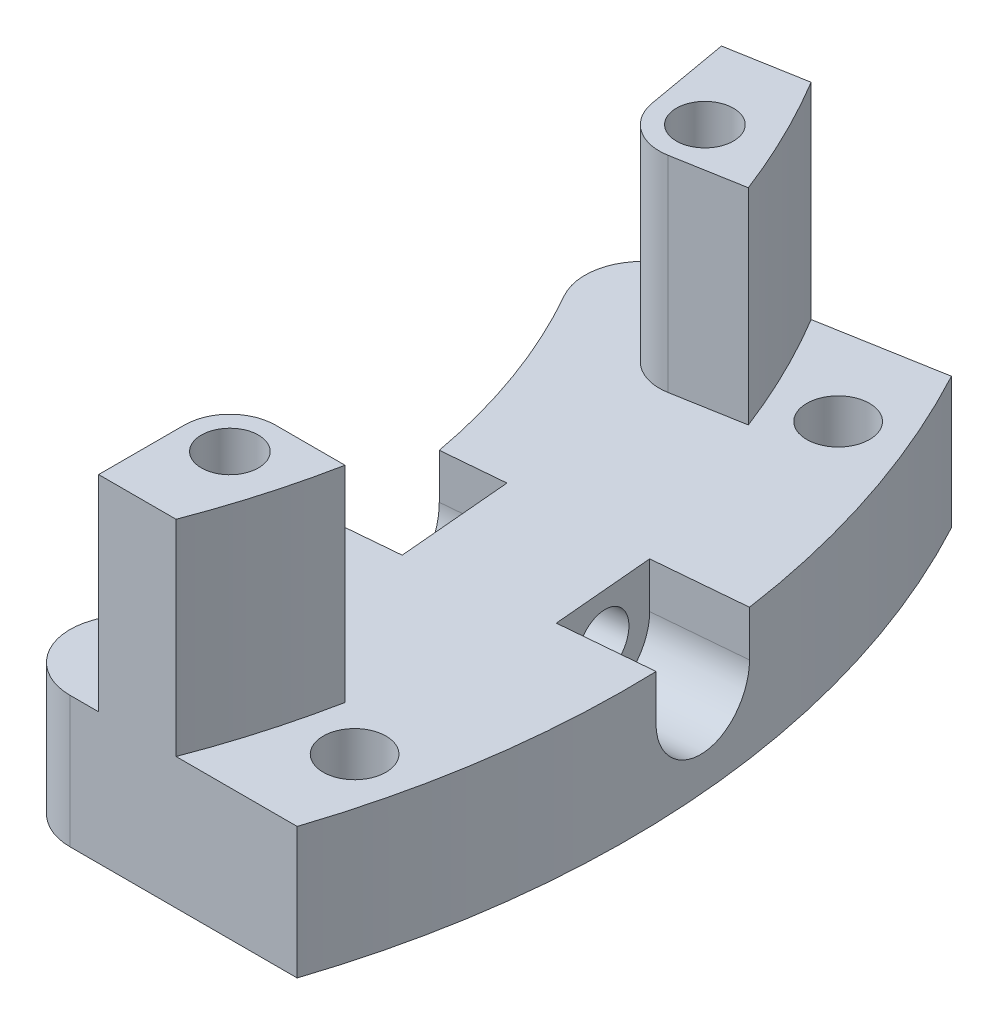
SolidWorks part; units mm, degrees
ref_plane "Front Plane" through (0, 0, 0) normal (0, 0, 1) x (1, 0, 0)
ref_plane "Top Plane" through (0, 0, 0) normal (0, 1, 0) x (1, 0, 0)
ref_plane "Right Plane" through (0, 0, 0) normal (1, 0, 0) x (0, 0, -1)
sketch "Sketch1" plane through (0, 0, 0) normal (0, 1, 0) x (1, 0, 0)
  line L0 (48.4934, -25) -> (75.9934, -25)
  line L1 (43.4155, 33.041) -> (70.4977, 37.8163)
  line L2 (0, -25) -> (48.4934, -25) construction
  line L3 (11.1696, 27.3552) -> (43.4155, 33.041) construction
  line L4 (-4.3412, 24.6202) -> (70.4977, 37.8163) construction
  arc A0 (70.4977, 37.8163) -> (75.9934, -25) centre (0, 0) cw
  arc A1 (43.4155, 33.041) -> (48.4934, -25) centre (0, 0) cw
  circle A2 centre (0, 0) radius 25 construction
  arc A3 (-4.3412, 24.6202) -> (0, -25) centre (0, 0) ccw construction
  point P3 (0, 0)
  point P9 (0, 32.5)
  point P10 (0, 0)
  point P13 (28.4664, 0.9627)
  point P17 (-8.5505, 23.4923)
  point P18 (10.6204, 30.47)
  dimension "D1" = 80
  dimension "D3" = 27.5
  dimension "D4" = 50
extrude "Boss-Extrude1" add sketch "Sketch1" along normal blind 11.5
sketch "Sketch2" plane through (0, 11.5, 0) normal (0, -1, 0) x (1, 0, 0)
  line L0 (48.4934, 25) -> (75.9934, 25) construction
  line L1 (70.4977, -37.8163) -> (43.4155, -33.041) construction
  line L2 (70.4977, -37.8163) -> (43.4155, -33.041) construction
  line L3 (62.5999, 13.5) -> (68.6859, 13.5)
  line L4 (58.5999, 17.5) -> (58.5999, 25)
  line L5 (48.4934, 25) -> (75.9934, 25) construction
  line L6 (58.5999, 25) -> (65.3835, 25)
  line L7 (54.6708, -27.4099) -> (53.3685, -34.796)
  line L8 (59.3046, -24.1653) -> (65.2981, -25.2221)
  line L9 (60.049, -35.9739) -> (53.3685, -34.796)
  arc A0 (65.3835, 25) -> (60.049, -35.9739) centre (0, 0) cw construction
  arc A1 (70.4977, -37.8163) -> (75.9934, 25) centre (0, 0) ccw construction
  arc A2 (58.5999, 17.5) -> (62.5999, 13.5) centre (62.5999, 17.5) ccw
  circle A3 centre (62.5999, 17.5) radius 5 construction
  arc A4 (59.3046, -24.1653) -> (54.6708, -27.4099) centre (58.61, -28.1045) ccw
  circle A5 centre (58.61, -28.1045) radius 5 construction
  arc A6 (65.3835, 25) -> (68.6859, 13.5) centre (0, 0) cw
  arc A7 (60.049, -35.9739) -> (65.2981, -25.2221) centre (0, 0) ccw
  dimension "D1" = 10
  dimension "D2" = 10
  dimension "D4" = 8
  dimension "D5" = 7.5
  dimension "D3" = 7.5
sketch "Sketch4" plane through (0, 0, 0) normal (0, -1, 0) x (1, 0, 0)
  circle A0 centre (73.0264, 17) radius 4.5
  circle A1 centre (68.965, -29.4226) radius 4.5
  circle A2 centre (73.0264, 17) radius 3.3 construction
  circle A3 centre (68.965, -29.4226) radius 3.3 construction
  dimension "D1" = 9
extrude "Cut-Extrude2" cut sketch "Sketch4" against normal blind 5
sketch "Sketch5" plane through (0, 5, 0) normal (0, -1, 0) x (1, 0, 0)
  circle A0 centre (73.0264, 17) radius 2.75
  circle A1 centre (68.965, -29.4226) radius 2.75
  dimension "D1" = 5.5
extrude "Cut-Extrude3" cut sketch "Sketch5" against normal through all
ref_plane "Plane1" through (45.9545, 0, -4.0205) normal (-0.9962, 0, 0.0872) x (0.0872, 0, 0.9962)
sketch "Sketch6" plane through (45.9545, 0, -4.0205) normal (-0.9962, 0, 0.0872) x (0.0872, 0, 0.9962)
  line L1 (29.1313, 11.5) -> (-29.1313, 11.5) construction
  circle A0 centre (0, 7.5) radius 5 construction
  circle A1 centre (0, 7.5) radius 2.5
  circle A2 centre (0, 7.5) radius 4.5 construction
  dimension "D1" = 10
  dimension "D2" = 4
  dimension "D3" = 5
  dimension "D4" = 9
extrude "Cut-Extrude4" cut sketch "Sketch6" against normal through all
ref_plane "Plane2" through (79.6956, 0, -6.9725) normal (0.9962, 0, -0.0872) x (-0.0872, 0, -0.9962)
ref_plane "Plane3" through (62.825, 0, -5.4965) normal (0.9962, 0, -0.0872) x (-0.0872, 0, -0.9962)
sketch "Sketch8" plane through (79.6956, 0, -6.9725) normal (0.9962, 0, -0.0872) x (-0.0872, 0, -0.9962)
  line L0 (-4.5, 7.5) -> (-4.5, 11.5)
  line L1 (31.5281, 11.5) -> (-31.5281, 11.5) construction
  line L2 (4.5, 7.5) -> (4.5, 11.5)
  line L3 (4.5, 11.5) -> (-4.5, 11.5)
  arc A1 (-4.5, 7.5) -> (4.5, 7.5) centre (0, 7.5) ccw
  dimension "D1" = 9
extrude "Cut-Extrude5" cut sketch "Sketch8" against normal blind 8.2
sketch "Sketch7" plane through (0, 11.5, 0) normal (0, 1, 0) x (1, 0, 0)
  line L1 (51.1627, 9.5455) -> (52.043, -0.5161) construction
  line L2 (0, 0) -> (51.6029, 4.5147) construction
  line L3 (51.1627, 9.5455) -> (76.0676, 11.7243) construction
  line L4 (76.0676, 11.7243) -> (76.9479, 1.6628) construction
  line L5 (76.9479, 1.6628) -> (52.043, -0.5161) construction
  line L7 (71.1346, 10.7407) -> (71.919, 1.7749) construction
  line L10 (51.1627, 9.5455) -> (52.043, -0.5161)
  line L11 (52.043, -0.5161) -> (60.0126, 0.1811)
  line L12 (60.0126, 0.1811) -> (59.1323, 10.2427)
  line L13 (59.1323, 10.2427) -> (51.1627, 9.5455)
  line L14 (71.0866, 11.2886) -> (71.9669, 1.227) construction
  line L15 (71.919, 1.7749) -> (71.1346, 10.7407) construction
  line L16 (48.4934, -25) -> (75.9934, -25) construction
  line L17 (70.4977, 37.8163) -> (43.4155, 33.041) construction
  arc A1 (70.4977, 37.8163) -> (75.9934, -25) centre (0, 0) cw construction
  point P0 (51.0498, 9.0015)
  point P15 (71.5268, 6.2578)
  dimension "D3" = 8
  dimension "D5" = 80
  dimension "D1" = 10.1
  dimension "D2" = 25
  dimension "D4" = 5
extrude "Cut-Extrude6" cut sketch "Sketch7" against normal blind 9
fillet "Fillet1" radius 5.05 2 edges at (57.2851, 2.5, 0.0575) (56.4048, 2.5, -10.0041)
fillet "Fillet2" radius 5 2 edges at (48.4934, 5.75, 25) (43.4155, 5.75, -33.041)
extrude "Boss-Extrude2" add sketch "Sketch2" against normal offset from surface (18 mm away) 22
sketch "Sketch3" plane through (0, 29.5, 0) normal (0, 1, 0) x (1, 0, 0)
  circle A0 centre (58.61, 28.1045) radius 2.5
  circle A1 centre (62.5999, -17.5) radius 2.5
  arc A2 (54.6708, 27.4099) -> (59.3046, 24.1653) centre (58.61, 28.1045) ccw construction
  arc A3 (62.5999, -13.5) -> (58.5999, -17.5) centre (62.5999, -17.5) ccw construction
  point P6 (0, 0)
  dimension "D1" = 5
extrude "Cut-Extrude1" cut sketch "Sketch3" against normal blind 4
